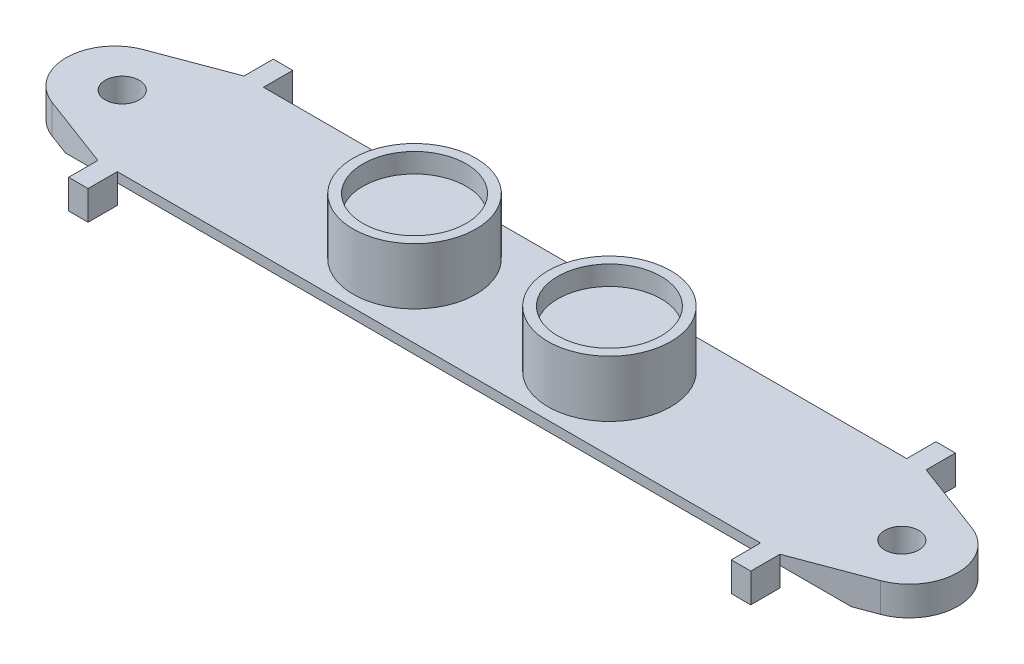
SolidWorks part; units mm, degrees
material "ABS"
ref_plane "Alzado" through (0, 0, 0) normal (0, 0, 1) x (1, 0, 0)
ref_plane "Planta" through (0, 0, 0) normal (0, 1, 0) x (1, 0, 0)
ref_plane "Vista lateral" through (0, 0, 0) normal (1, 0, 0) x (0, 0, -1)
sketch "Sketch1" plane through (0, 0, 0) normal (0, 1, 0) x (1, 0, 0)
  line L0 (35, 7.5) -> (55, 0)
  line L1 (-35, 7.5) -> (35, 7.5)
  line L3 (-35, -7.5) -> (35, -7.5)
  line L5 (-35, 7.5) -> (35, -7.5) construction
  line L6 (-35, -7.5) -> (35, 7.5) construction
  line L7 (55, 0) -> (35, -7.5)
  line L8 (-35, 7.5) -> (-55, 0)
  line L9 (-55, 0) -> (-35, -7.5)
  line L10 (-35, 7.5) -> (-35, -7.5) construction
  line L11 (35, 7.5) -> (35, -7.5) construction
  line L12 (0, 7.5) -> (0, -7.5) construction
  circle A0 centre (-40, 0) radius 1.75
  circle A1 centre (40, 0) radius 1.75
  point P0 (0, 0)
  dimension "D4" = 40
  dimension "D5" = 3.5
  dimension "D1" = 110
  dimension "D2" = 70
  dimension "D3" = 15
extrude "Boss-Extrude1" add sketch "Sketch1" along normal blind 3
sketch "Sketch2" plane through (0, 3, 0) normal (0, 1, 0) x (1, 0, 0)
  line L0 (0, 7.5) -> (0, -7.5) construction
  line L1 (35, 7.5) -> (-35, 7.5) construction
  line L2 (-35, -7.5) -> (35, -7.5) construction
  circle A1 centre (10, 0) radius 6.3
  circle A2 centre (-10, 0) radius 6.3
  dimension "D1" = 10
  dimension "D2" = 12.6
extrude "Boss-Extrude2" add sketch "Sketch2" along normal blind 3.8
sketch "Sketch3" plane through (0, 6.8, 0) normal (0, 1, 0) x (1, 0, 0)
  circle A0 centre (-10, 0) radius 6.3
  circle A1 centre (10, 0) radius 6.3
  circle A2 centre (-10, 0) radius 5.3
  circle A3 centre (10, 0) radius 5.3
  dimension "D1" = 10.6
extrude "Boss-Extrude3" add sketch "Sketch3" along normal blind 2
fillet "Fillet1" radius 5 2 edges at (55, 1.5, 0) (-55, 1.5, 0)
chamfer "Chamfer1" distance 2 angle 45 2 edges at (0, 0, -7.5) (0, 0, 7.5)
sketch "Sketch5" plane through (0, 3, 0) normal (0, 1, 0) x (1, 0, 0)
  line L0 (0, 7.5) -> (0, -7.5) construction
  line L1 (-35, 7.5) -> (-33, 7.5)
  line L2 (-35, 7.5) -> (-35, 10.5)
  line L3 (-35, 10.5) -> (-33, 10.5)
  line L4 (-33, 7.5) -> (-33, 10.5)
  line L5 (35, 7.5) -> (-35, 7.5) construction
  line L6 (-35, -7.5) -> (35, -7.5) construction
  line L7 (35, -10.5) -> (33, -10.5)
  line L8 (-35, -7.5) -> (-33, -7.5)
  line L9 (-35, -7.5) -> (-35, -10.5)
  line L10 (-35, -10.5) -> (-33, -10.5)
  line L11 (-33, -7.5) -> (-33, -10.5)
  line L12 (33, -7.5) -> (33, -10.5)
  line L13 (35, -7.5) -> (33, -7.5)
  line L14 (35, -7.5) -> (35, -10.5)
  line L15 (35, 10.5) -> (33, 10.5)
  line L16 (33, 7.5) -> (33, 10.5)
  line L17 (35, 7.5) -> (33, 7.5)
  line L18 (35, 7.5) -> (35, 10.5)
  dimension "D1" = 2
  dimension "D2" = 3
extrude "Boss-Extrude4" add sketch "Sketch5" against normal blind 3
